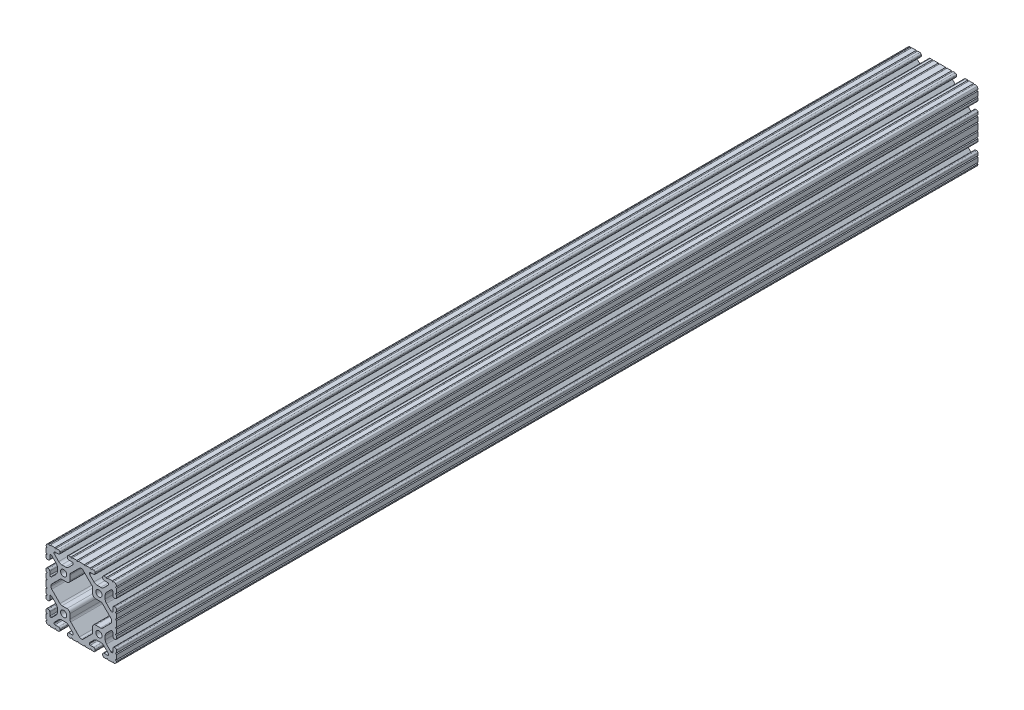
SolidWorks part; units mm, degrees
ref_plane "Front Plane" through (0, 0, 0) normal (0, 0, 1) x (1, 0, 0)
ref_plane "Top Plane" through (0, 0, 0) normal (0, 1, 0) x (1, 0, 0)
ref_plane "Right Plane" through (0, 0, 0) normal (1, 0, 0) x (0, 0, -1)
sketch "Sketch1" plane through (0, 0, 0) normal (0, 0, 1) x (1, 0, 0)
  line L0 (0, 38.1) -> (0, -38.1) construction
  line L1 (-38.1, -38.1) -> (38.1, -38.1) construction
  line L2 (-38.1, -38.1) -> (-38.1, 38.1) construction
  line L3 (-38.1, 38.1) -> (38.1, 38.1) construction
  line L4 (38.1, -38.1) -> (38.1, 38.1) construction
  line L5 (0, 38.1) -> (0, -38.1) construction
  line L6 (-38.1, 0) -> (38.1, 0) construction
  line L7 (-19.05, 19.05) -> (19.05, 19.05) construction
  line L8 (-19.05, 19.05) -> (-19.05, -19.05) construction
  line L9 (-19.05, -19.05) -> (19.05, -19.05) construction
  line L10 (19.05, 19.05) -> (19.05, -19.05) construction
  line L11 (-23.114, 38.1) -> (-23.114, -38.1) construction
  line L12 (-23.114, -38.1) -> (-14.986, 38.1) construction
  line L13 (-14.986, 38.1) -> (-14.986, -38.1) construction
  circle A0 centre (19.05, 19.05) radius 3.3274
  point P0 (0, 0)
  point P9 (0, 0)
  point P12 (-19.05, 0)
  line B0 (-11.3637, -22.8433) -> (-2.0515, -32.1555)
  line B1 (-12.2936, -15.4686) -> (-12.2936, -20.5983)
  line B2 (-20.769, -12.2936) -> (-15.4686, -12.2936)
  line B3 (-31.9021, -2.4756) -> (-23.0141, -11.3637)
  line B4 (-23.0141, 11.3637) -> (-31.9021, 2.4756)
  line B5 (-15.4686, 12.2936) -> (-20.769, 12.2936)
  line B6 (-12.2936, 20.5983) -> (-12.2936, 15.4686)
  line B7 (-2.0515, 32.1555) -> (-11.3637, 22.8433)
  line B8 (11.3637, 22.8433) -> (2.0515, 32.1555)
  line B9 (12.2936, 15.4686) -> (12.2936, 20.5983)
  line B10 (20.769, 12.2936) -> (15.4686, 12.2936)
  line B11 (31.9021, 2.4756) -> (23.0141, 11.3637)
  line B12 (23.0141, -11.3637) -> (31.9021, -2.4756)
  line B13 (15.4686, -12.2936) -> (20.769, -12.2936)
  line B14 (12.2936, -20.5983) -> (12.2936, -15.4686)
  line B15 (2.0515, -32.1555) -> (11.3637, -22.8433)
  line B16 (-4.7773, 38.1) -> (-9.6053, 38.1)
  line B17 (-11.1289, 38.1) -> (-13.4112, 38.1)
  line B18 (-14.986, 36.5252) -> (-14.986, 35.6108)
  line B19 (-13.4112, 34.036) -> (-9.652, 34.036)
  line B20 (-8.763, 33.147) -> (-8.763, 32.4935)
  line B21 (-9.0234, 31.8649) -> (-13.6907, 27.1976)
  line B22 (-17.0493, 25.8064) -> (-21.0507, 25.8064)
  line B23 (-24.4093, 27.1976) -> (-29.1002, 31.8885)
  line B24 (-29.337, 32.7207) -> (-29.337, 33.147)
  line B25 (-28.448, 34.036) -> (-24.6888, 34.036)
  line B26 (-23.114, 35.6108) -> (-23.114, 36.5252)
  line B27 (-24.6888, 38.1) -> (-27.0772, 38.1)
  line B28 (-28.6011, 38.1) -> (-33.4288, 38.1)
  line B29 (-38.1, 33.373) -> (-38.1, 28.5453)
  line B30 (-38.1, 27.0238) -> (-38.1, 24.6302)
  line B31 (-36.5252, 23.0554) -> (-35.6108, 23.0554)
  line B32 (-34.036, 24.6302) -> (-34.036, 28.448)
  line B33 (-33.147, 29.337) -> (-32.6643, 29.337)
  line B34 (-32.0357, 29.0766) -> (-27.1976, 24.2385)
  line B35 (-25.8064, 20.8799) -> (-25.8064, 17.2201)
  line B36 (-27.1976, 13.8615) -> (-31.9489, 9.1101)
  line B37 (-32.7869, 8.763) -> (-33.0603, 8.763)
  line B38 (-34.036, 9.7387) -> (-34.036, 13.4698)
  line B39 (-35.6108, 15.0446) -> (-36.5252, 15.0446)
  line B40 (-38.1, 13.4698) -> (-38.1, 11.075)
  line B41 (-38.1, 9.552) -> (-38.1, 4.7238)
  line B42 (-38.1, 3.2007) -> (-38.1, -3.2007)
  line B43 (-38.1, -4.7238) -> (-38.1, -9.552)
  line B44 (-38.1, -11.075) -> (-38.1, -13.4698)
  line B45 (-36.5252, -15.0446) -> (-35.6108, -15.0446)
  line B46 (-34.036, -13.4698) -> (-34.036, -9.7387)
  line B47 (-33.0603, -8.763) -> (-32.7869, -8.763)
  line B48 (-31.9489, -9.1101) -> (-27.1976, -13.8615)
  line B49 (-25.8064, -17.2201) -> (-25.8064, -20.8799)
  line B50 (-27.1976, -24.2385) -> (-32.0357, -29.0766)
  line B51 (-32.6643, -29.337) -> (-33.147, -29.337)
  line B52 (-34.036, -28.448) -> (-34.036, -24.6302)
  line B53 (-35.6108, -23.0554) -> (-36.5252, -23.0554)
  line B54 (-38.1, -24.6302) -> (-38.1, -27.0238)
  line B55 (-38.1, -28.5453) -> (-38.1, -33.373)
  line B56 (-33.4288, -38.1) -> (-28.6011, -38.1)
  line B57 (-27.0772, -38.1) -> (-24.6888, -38.1)
  line B58 (-23.114, -36.5252) -> (-23.114, -35.6108)
  line B59 (-24.6888, -34.036) -> (-28.448, -34.036)
  line B60 (-29.337, -33.147) -> (-29.337, -32.7207)
  line B61 (-29.1002, -31.8885) -> (-24.4093, -27.1976)
  line B62 (-21.0507, -25.8064) -> (-17.0493, -25.8064)
  line B63 (-13.6907, -27.1976) -> (-9.0234, -31.8649)
  line B64 (-8.763, -32.4935) -> (-8.763, -33.147)
  line B65 (-9.652, -34.036) -> (-13.4112, -34.036)
  line B66 (-14.986, -35.6108) -> (-14.986, -36.5252)
  line B67 (-13.4112, -38.1) -> (-11.1289, -38.1)
  line B68 (-9.6053, -38.1) -> (-4.7773, -38.1)
  line B69 (-3.2537, -38.1) -> (3.2537, -38.1)
  line B70 (4.7773, -38.1) -> (9.6053, -38.1)
  line B71 (11.1289, -38.1) -> (13.4112, -38.1)
  line B72 (14.986, -36.5252) -> (14.986, -35.6108)
  line B73 (13.4112, -34.036) -> (9.652, -34.036)
  line B74 (8.763, -33.147) -> (8.763, -32.4935)
  line B75 (9.0234, -31.8649) -> (13.6907, -27.1976)
  line B76 (17.0493, -25.8064) -> (21.0507, -25.8064)
  line B77 (24.4093, -27.1976) -> (29.1002, -31.8885)
  line B78 (29.337, -32.7207) -> (29.337, -33.147)
  line B79 (28.448, -34.036) -> (24.6888, -34.036)
  line B80 (23.114, -35.6108) -> (23.114, -36.5252)
  line B81 (24.6888, -38.1) -> (27.0772, -38.1)
  line B82 (28.6011, -38.1) -> (33.4288, -38.1)
  line B83 (38.1, -33.373) -> (38.1, -28.5453)
  line B84 (38.1, -27.0238) -> (38.1, -24.6302)
  line B85 (36.5252, -23.0554) -> (35.6108, -23.0554)
  line B86 (34.036, -24.6302) -> (34.036, -28.448)
  line B87 (33.147, -29.337) -> (32.6643, -29.337)
  line B88 (32.0357, -29.0766) -> (27.1976, -24.2385)
  line B89 (25.8064, -20.8799) -> (25.8064, -17.2201)
  line B90 (27.1976, -13.8615) -> (31.9489, -9.1101)
  line B91 (32.7869, -8.763) -> (33.0603, -8.763)
  line B92 (34.036, -9.7387) -> (34.036, -13.4698)
  line B93 (35.6108, -15.0446) -> (36.5252, -15.0446)
  line B94 (38.1, -13.4698) -> (38.1, -11.075)
  line B95 (38.1, -9.552) -> (38.1, -4.7238)
  line B96 (38.1, -3.2007) -> (38.1, 3.2007)
  line B97 (38.1, 4.7238) -> (38.1, 9.552)
  line B98 (38.1, 11.075) -> (38.1, 13.4698)
  line B99 (36.5252, 15.0446) -> (35.6108, 15.0446)
  line B100 (34.036, 13.4698) -> (34.036, 9.7387)
  line B101 (33.0603, 8.763) -> (32.7869, 8.763)
  line B102 (31.9489, 9.1101) -> (27.1976, 13.8615)
  line B103 (25.8064, 17.2201) -> (25.8064, 20.8799)
  line B104 (27.1976, 24.2385) -> (32.0357, 29.0766)
  line B105 (32.6643, 29.337) -> (33.147, 29.337)
  line B106 (34.036, 28.448) -> (34.036, 24.6302)
  line B107 (35.6108, 23.0554) -> (36.5252, 23.0554)
  line B108 (38.1, 24.6302) -> (38.1, 27.0238)
  line B109 (38.1, 28.5453) -> (38.1, 33.373)
  line B110 (33.4288, 38.1) -> (28.6011, 38.1)
  line B111 (27.0772, 38.1) -> (24.6888, 38.1)
  line B112 (23.114, 36.5252) -> (23.114, 35.6108)
  line B113 (24.6888, 34.036) -> (28.448, 34.036)
  line B114 (29.337, 33.147) -> (29.337, 32.7207)
  line B115 (29.1002, 31.8885) -> (24.4093, 27.1976)
  line B116 (21.0507, 25.8064) -> (17.0493, 25.8064)
  line B117 (13.6907, 27.1976) -> (9.0234, 31.8649)
  line B118 (8.763, 32.4935) -> (8.763, 33.147)
  line B119 (9.652, 34.036) -> (13.4112, 34.036)
  line B120 (14.986, 35.6108) -> (14.986, 36.5252)
  line B121 (13.4112, 38.1) -> (11.1289, 38.1)
  line B122 (9.6053, 38.1) -> (4.7773, 38.1)
  line B123 (3.2537, 38.1) -> (-3.2537, 38.1)
  circle B124 centre (-19.05, 19.05) radius 3.3274
  circle B125 centre (-19.05, -19.05) radius 3.3274
  circle B126 centre (19.05, -19.05) radius 3.3274
  circle B127 centre (19.05, 19.05) radius 3.3274
  arc B128 (0, -33.011) -> (2.0515, -32.1555) centre (-0.0139, -30.09) ccw
  arc B129 (-2.0515, -32.1555) -> (0, -33.011) centre (0.0139, -30.09) ccw
  arc B130 (-12.2936, -20.5983) -> (-11.3637, -22.8433) centre (-9.1186, -20.5983) ccw
  arc B131 (-12.2936, -15.4686) -> (-15.4686, -12.2936) centre (-15.4686, -15.4686) ccw
  arc B132 (-23.0141, -11.3637) -> (-20.769, -12.2936) centre (-20.769, -9.1186) ccw
  arc B133 (-32.7287, 0) -> (-31.9021, -2.4756) centre (-29.8367, -0.4102) ccw
  arc B134 (-31.9021, 2.4756) -> (-32.7287, 0) centre (-29.8367, 0.4102) ccw
  arc B135 (-20.769, 12.2936) -> (-23.0141, 11.3637) centre (-20.769, 9.1186) ccw
  arc B136 (-15.4686, 12.2936) -> (-12.2936, 15.4686) centre (-15.4686, 15.4686) ccw
  arc B137 (-11.3637, 22.8433) -> (-12.2936, 20.5983) centre (-9.1186, 20.5983) ccw
  arc B138 (0, 33.011) -> (-2.0515, 32.1555) centre (0.0139, 30.09) ccw
  arc B139 (2.0515, 32.1555) -> (0, 33.011) centre (-0.0139, 30.09) ccw
  arc B140 (12.2936, 20.5983) -> (11.3637, 22.8433) centre (9.1186, 20.5983) ccw
  arc B141 (12.2936, 15.4686) -> (15.4686, 12.2936) centre (15.4686, 15.4686) ccw
  arc B142 (23.0141, 11.3637) -> (20.769, 12.2936) centre (20.769, 9.1186) ccw
  arc B143 (32.7287, 0) -> (31.9021, 2.4756) centre (29.8367, 0.4102) ccw
  arc B144 (31.9021, -2.4756) -> (32.7287, 0) centre (29.8367, -0.4102) ccw
  arc B145 (20.769, -12.2936) -> (23.0141, -11.3637) centre (20.769, -9.1186) ccw
  arc B146 (15.4686, -12.2936) -> (12.2936, -15.4686) centre (15.4686, -15.4686) ccw
  arc B147 (11.3637, -22.8433) -> (12.2936, -20.5983) centre (9.1186, -20.5983) ccw
  arc B148 (-4.7773, 38.1) -> (-3.2537, 38.1) centre (-4.0155, 38.0824) ccw
  arc B149 (-11.1289, 38.1) -> (-9.6053, 38.1) centre (-10.3671, 38.0824) ccw
  arc B150 (-13.4112, 38.1) -> (-14.986, 36.5252) centre (-13.4112, 36.5252) ccw
  arc B151 (-14.986, 35.6108) -> (-13.4112, 34.036) centre (-13.4112, 35.6108) ccw
  arc B152 (-8.763, 33.147) -> (-9.652, 34.036) centre (-9.652, 33.147) ccw
  arc B153 (-9.0234, 31.8649) -> (-8.763, 32.4935) centre (-9.652, 32.4935) ccw
  arc B154 (-17.0493, 25.8064) -> (-13.6907, 27.1976) centre (-17.0493, 30.5562) ccw
  arc B155 (-24.4093, 27.1976) -> (-21.0507, 25.8064) centre (-21.0507, 30.5562) ccw
  arc B156 (-29.337, 32.7207) -> (-29.1002, 31.8885) centre (-28.4716, 32.5172) ccw
  arc B157 (-28.448, 34.036) -> (-29.337, 33.147) centre (-28.448, 33.147) ccw
  arc B158 (-24.6888, 34.036) -> (-23.114, 35.6108) centre (-24.6888, 35.6108) ccw
  arc B159 (-23.114, 36.5252) -> (-24.6888, 38.1) centre (-24.6888, 36.5252) ccw
  arc B160 (-28.6011, 38.1) -> (-27.0772, 38.1) centre (-27.8392, 38.0824) ccw
  arc B161 (-34.9527, 38.1) -> (-33.4288, 38.1) centre (-34.1907, 38.0824) ccw
  arc B162 (-34.9527, 38.1) -> (-37.0861, 37.1826) centre (-34.8521, 34.9266) ccw
  arc B163 (-37.0861, 37.1826) -> (-38.1, 34.8455) centre (-34.925, 34.8566) ccw
  arc B164 (-38.1, 33.373) -> (-38.1, 34.8455) centre (-37.9035, 34.1092) ccw
  arc B165 (-38.1, 27.0238) -> (-38.1, 28.5453) centre (-37.9035, 27.7845) ccw
  arc B166 (-38.1, 24.6302) -> (-36.5252, 23.0554) centre (-36.5252, 24.6302) ccw
  arc B167 (-35.6108, 23.0554) -> (-34.036, 24.6302) centre (-35.6108, 24.6302) ccw
  arc B168 (-33.147, 29.337) -> (-34.036, 28.448) centre (-33.147, 28.448) ccw
  arc B169 (-32.0357, 29.0766) -> (-32.6643, 29.337) centre (-32.6643, 28.448) ccw
  arc B170 (-25.8064, 20.8799) -> (-27.1976, 24.2385) centre (-30.5562, 20.8799) ccw
  arc B171 (-27.1976, 13.8615) -> (-25.8064, 17.2201) centre (-30.5562, 17.2201) ccw
  arc B172 (-32.7869, 8.763) -> (-31.9489, 9.1101) centre (-32.7869, 9.9481) ccw
  arc B173 (-34.036, 9.7387) -> (-33.0603, 8.763) centre (-33.0603, 9.7387) ccw
  arc B174 (-34.036, 13.4698) -> (-35.6108, 15.0446) centre (-35.6108, 13.4698) ccw
  arc B175 (-36.5252, 15.0446) -> (-38.1, 13.4698) centre (-36.5252, 13.4698) ccw
  arc B176 (-38.1, 9.552) -> (-38.1, 11.075) centre (-37.9035, 10.3135) ccw
  arc B177 (-38.1, 3.2007) -> (-38.1, 4.7238) centre (-37.9035, 3.9622) ccw
  arc B178 (-38.1, -4.7238) -> (-38.1, -3.2007) centre (-37.9035, -3.9622) ccw
  arc B179 (-38.1, -11.075) -> (-38.1, -9.552) centre (-37.9035, -10.3135) ccw
  arc B180 (-38.1, -13.4698) -> (-36.5252, -15.0446) centre (-36.5252, -13.4698) ccw
  arc B181 (-35.6108, -15.0446) -> (-34.036, -13.4698) centre (-35.6108, -13.4698) ccw
  arc B182 (-33.0603, -8.763) -> (-34.036, -9.7387) centre (-33.0603, -9.7387) ccw
  arc B183 (-31.9489, -9.1101) -> (-32.7869, -8.763) centre (-32.7869, -9.9481) ccw
  arc B184 (-25.8064, -17.2201) -> (-27.1976, -13.8615) centre (-30.5562, -17.2201) ccw
  arc B185 (-27.1976, -24.2385) -> (-25.8064, -20.8799) centre (-30.5562, -20.8799) ccw
  arc B186 (-32.6643, -29.337) -> (-32.0357, -29.0766) centre (-32.6643, -28.448) ccw
  arc B187 (-34.036, -28.448) -> (-33.147, -29.337) centre (-33.147, -28.448) ccw
  arc B188 (-34.036, -24.6302) -> (-35.6108, -23.0554) centre (-35.6108, -24.6302) ccw
  arc B189 (-36.5252, -23.0554) -> (-38.1, -24.6302) centre (-36.5252, -24.6302) ccw
  arc B190 (-38.1, -28.5453) -> (-38.1, -27.0238) centre (-37.9035, -27.7845) ccw
  arc B191 (-38.1, -34.8455) -> (-38.1, -33.373) centre (-37.9035, -34.1092) ccw
  arc B192 (-38.1, -34.8455) -> (-37.0861, -37.1826) centre (-34.925, -34.8566) ccw
  arc B193 (-37.0861, -37.1826) -> (-34.9527, -38.1) centre (-34.8521, -34.9266) ccw
  arc B194 (-33.4288, -38.1) -> (-34.9527, -38.1) centre (-34.1907, -38.0824) ccw
  arc B195 (-27.0772, -38.1) -> (-28.6011, -38.1) centre (-27.8392, -38.0824) ccw
  arc B196 (-24.6888, -38.1) -> (-23.114, -36.5252) centre (-24.6888, -36.5252) ccw
  arc B197 (-23.114, -35.6108) -> (-24.6888, -34.036) centre (-24.6888, -35.6108) ccw
  arc B198 (-29.337, -33.147) -> (-28.448, -34.036) centre (-28.448, -33.147) ccw
  arc B199 (-29.1002, -31.8885) -> (-29.337, -32.7207) centre (-28.4716, -32.5172) ccw
  arc B200 (-21.0507, -25.8064) -> (-24.4093, -27.1976) centre (-21.0507, -30.5562) ccw
  arc B201 (-13.6907, -27.1976) -> (-17.0493, -25.8064) centre (-17.0493, -30.5562) ccw
  arc B202 (-8.763, -32.4935) -> (-9.0234, -31.8649) centre (-9.652, -32.4935) ccw
  arc B203 (-9.652, -34.036) -> (-8.763, -33.147) centre (-9.652, -33.147) ccw
  arc B204 (-13.4112, -34.036) -> (-14.986, -35.6108) centre (-13.4112, -35.6108) ccw
  arc B205 (-14.986, -36.5252) -> (-13.4112, -38.1) centre (-13.4112, -36.5252) ccw
  arc B206 (-9.6053, -38.1) -> (-11.1289, -38.1) centre (-10.3671, -38.0824) ccw
  arc B207 (-3.2537, -38.1) -> (-4.7773, -38.1) centre (-4.0155, -38.0824) ccw
  arc B208 (4.7773, -38.1) -> (3.2537, -38.1) centre (4.0155, -38.0824) ccw
  arc B209 (11.1289, -38.1) -> (9.6053, -38.1) centre (10.3671, -38.0824) ccw
  arc B210 (13.4112, -38.1) -> (14.986, -36.5252) centre (13.4112, -36.5252) ccw
  arc B211 (14.986, -35.6108) -> (13.4112, -34.036) centre (13.4112, -35.6108) ccw
  arc B212 (8.763, -33.147) -> (9.652, -34.036) centre (9.652, -33.147) ccw
  arc B213 (9.0234, -31.8649) -> (8.763, -32.4935) centre (9.652, -32.4935) ccw
  arc B214 (17.0493, -25.8064) -> (13.6907, -27.1976) centre (17.0493, -30.5562) ccw
  arc B215 (24.4093, -27.1976) -> (21.0507, -25.8064) centre (21.0507, -30.5562) ccw
  arc B216 (29.337, -32.7207) -> (29.1002, -31.8885) centre (28.4716, -32.5172) ccw
  arc B217 (28.448, -34.036) -> (29.337, -33.147) centre (28.448, -33.147) ccw
  arc B218 (24.6888, -34.036) -> (23.114, -35.6108) centre (24.6888, -35.6108) ccw
  arc B219 (23.114, -36.5252) -> (24.6888, -38.1) centre (24.6888, -36.5252) ccw
  arc B220 (28.6011, -38.1) -> (27.0772, -38.1) centre (27.8392, -38.0824) ccw
  arc B221 (34.9527, -38.1) -> (33.4288, -38.1) centre (34.1907, -38.0824) ccw
  arc B222 (34.9527, -38.1) -> (37.0861, -37.1826) centre (34.8521, -34.9266) ccw
  arc B223 (37.0861, -37.1826) -> (38.1, -34.8455) centre (34.925, -34.8566) ccw
  arc B224 (38.1, -33.373) -> (38.1, -34.8455) centre (37.9035, -34.1092) ccw
  arc B225 (38.1, -27.0238) -> (38.1, -28.5453) centre (37.9035, -27.7845) ccw
  arc B226 (38.1, -24.6302) -> (36.5252, -23.0554) centre (36.5252, -24.6302) ccw
  arc B227 (35.6108, -23.0554) -> (34.036, -24.6302) centre (35.6108, -24.6302) ccw
  arc B228 (33.147, -29.337) -> (34.036, -28.448) centre (33.147, -28.448) ccw
  arc B229 (32.0357, -29.0766) -> (32.6643, -29.337) centre (32.6643, -28.448) ccw
  arc B230 (25.8064, -20.8799) -> (27.1976, -24.2385) centre (30.5562, -20.8799) ccw
  arc B231 (27.1976, -13.8615) -> (25.8064, -17.2201) centre (30.5562, -17.2201) ccw
  arc B232 (32.7869, -8.763) -> (31.9489, -9.1101) centre (32.7869, -9.9481) ccw
  arc B233 (34.036, -9.7387) -> (33.0603, -8.763) centre (33.0603, -9.7387) ccw
  arc B234 (34.036, -13.4698) -> (35.6108, -15.0446) centre (35.6108, -13.4698) ccw
  arc B235 (36.5252, -15.0446) -> (38.1, -13.4698) centre (36.5252, -13.4698) ccw
  arc B236 (38.1, -9.552) -> (38.1, -11.075) centre (37.9035, -10.3135) ccw
  arc B237 (38.1, -3.2007) -> (38.1, -4.7238) centre (37.9035, -3.9622) ccw
  arc B238 (38.1, 4.7238) -> (38.1, 3.2007) centre (37.9035, 3.9622) ccw
  arc B239 (38.1, 11.075) -> (38.1, 9.552) centre (37.9035, 10.3135) ccw
  arc B240 (38.1, 13.4698) -> (36.5252, 15.0446) centre (36.5252, 13.4698) ccw
  arc B241 (35.6108, 15.0446) -> (34.036, 13.4698) centre (35.6108, 13.4698) ccw
  arc B242 (33.0603, 8.763) -> (34.036, 9.7387) centre (33.0603, 9.7387) ccw
  arc B243 (31.9489, 9.1101) -> (32.7869, 8.763) centre (32.7869, 9.9481) ccw
  arc B244 (25.8064, 17.2201) -> (27.1976, 13.8615) centre (30.5562, 17.2201) ccw
  arc B245 (27.1976, 24.2385) -> (25.8064, 20.8799) centre (30.5562, 20.8799) ccw
  arc B246 (32.6643, 29.337) -> (32.0357, 29.0766) centre (32.6643, 28.448) ccw
  arc B247 (34.036, 28.448) -> (33.147, 29.337) centre (33.147, 28.448) ccw
  arc B248 (34.036, 24.6302) -> (35.6108, 23.0554) centre (35.6108, 24.6302) ccw
  arc B249 (36.5252, 23.0554) -> (38.1, 24.6302) centre (36.5252, 24.6302) ccw
  arc B250 (38.1, 28.5453) -> (38.1, 27.0238) centre (37.9035, 27.7845) ccw
  arc B251 (38.1, 34.8455) -> (38.1, 33.373) centre (37.9035, 34.1092) ccw
  arc B252 (38.1, 34.8455) -> (37.0861, 37.1826) centre (34.925, 34.8566) ccw
  arc B253 (37.0861, 37.1826) -> (34.9527, 38.1) centre (34.8521, 34.9266) ccw
  arc B254 (33.4288, 38.1) -> (34.9527, 38.1) centre (34.1907, 38.0824) ccw
  arc B255 (27.0772, 38.1) -> (28.6011, 38.1) centre (27.8392, 38.0824) ccw
  arc B256 (24.6888, 38.1) -> (23.114, 36.5252) centre (24.6888, 36.5252) ccw
  arc B257 (23.114, 35.6108) -> (24.6888, 34.036) centre (24.6888, 35.6108) ccw
  arc B258 (29.337, 33.147) -> (28.448, 34.036) centre (28.448, 33.147) ccw
  arc B259 (29.1002, 31.8885) -> (29.337, 32.7207) centre (28.4716, 32.5172) ccw
  arc B260 (21.0507, 25.8064) -> (24.4093, 27.1976) centre (21.0507, 30.5562) ccw
  arc B261 (13.6907, 27.1976) -> (17.0493, 25.8064) centre (17.0493, 30.5562) ccw
  arc B262 (8.763, 32.4935) -> (9.0234, 31.8649) centre (9.652, 32.4935) ccw
  arc B263 (9.652, 34.036) -> (8.763, 33.147) centre (9.652, 33.147) ccw
  arc B264 (13.4112, 34.036) -> (14.986, 35.6108) centre (13.4112, 35.6108) ccw
  arc B265 (14.986, 36.5252) -> (13.4112, 38.1) centre (13.4112, 36.5252) ccw
  arc B266 (9.6053, 38.1) -> (11.1289, 38.1) centre (10.3671, 38.0824) ccw
  arc B267 (3.2537, 38.1) -> (4.7773, 38.1) centre (4.0155, 38.0824) ccw
  dimension "Center Hole Diameter" = 6.6548
  dimension "Rail Width" = 76.2
  dimension "Rail Height" = 76.2
  dimension "T-Slot Width" = 8.128
sketch_block_instance "Block1-1"
sketch_block "Block1"
sketch "Sketch2" plane through (0, 0, 0) normal (1, 0, 0) x (0, 0, -1)
  line L0 (-465, 0) -> (465, 0) construction
  line L1 (-465, 38.1) -> (-465, -38.1) construction
  line L2 (-465, -38.1) -> (465, -38.1) construction
  line L3 (465, -38.1) -> (465, 38.1) construction
  line L4 (-363.4, 0) -> (-363.4, 38.1) construction
  line L5 (-363.4, 38.1) -> (363.4, 38.1) construction
  line L6 (363.4, 38.1) -> (363.4, 0) construction
  point P5 (363.4, 0)
  point P10 (-363.4, 0)
  dimension "D1" = 101.6
  dimension "Length" = 930
  dimension "D2" = 101.6
sketch "Sketch3" plane through (0, 0, 0) normal (0, 0, 1) x (1, 0, 0)
  line L0 (-11.3637, -22.8433) -> (-2.0515, -32.1555) construction
  line L1 (-12.2936, -15.4686) -> (-12.2936, -20.5983) construction
  line L2 (-20.769, -12.2936) -> (-15.4686, -12.2936) construction
  line L3 (-31.9021, -2.4756) -> (-23.0141, -11.3637) construction
  line L4 (-23.0141, 11.3637) -> (-31.9021, 2.4756) construction
  line L5 (-15.4686, 12.2936) -> (-20.769, 12.2936) construction
  line L6 (-12.2936, 20.5983) -> (-12.2936, 15.4686) construction
  line L7 (-2.0515, 32.1555) -> (-11.3637, 22.8433) construction
  line L8 (11.3637, 22.8433) -> (2.0515, 32.1555) construction
  line L9 (12.2936, 15.4686) -> (12.2936, 20.5983) construction
  line L10 (20.769, 12.2936) -> (15.4686, 12.2936) construction
  line L11 (31.9021, 2.4756) -> (23.0141, 11.3637) construction
  line L12 (23.0141, -11.3637) -> (31.9021, -2.4756) construction
  line L13 (15.4686, -12.2936) -> (20.769, -12.2936) construction
  line L14 (12.2936, -20.5983) -> (12.2936, -15.4686) construction
  line L15 (2.0515, -32.1555) -> (11.3637, -22.8433) construction
  line L16 (34.036, 28.448) -> (34.036, 24.6302) construction
  line L17 (35.6108, 23.0554) -> (36.5252, 23.0554) construction
  line L18 (38.1, 24.6302) -> (38.1, 27.0238) construction
  line L19 (38.1, 28.5453) -> (38.1, 33.373) construction
  line L20 (33.4288, 38.1) -> (28.6011, 38.1) construction
  line L21 (27.0772, 38.1) -> (24.6888, 38.1) construction
  line L22 (23.114, 36.5252) -> (23.114, 35.6108) construction
  line L23 (24.6888, 34.036) -> (28.448, 34.036) construction
  line L24 (29.337, 33.147) -> (29.337, 32.7207) construction
  line L25 (29.1002, 31.8885) -> (24.4093, 27.1976) construction
  line L26 (21.0507, 25.8064) -> (17.0493, 25.8064) construction
  line L27 (13.6907, 27.1976) -> (9.0234, 31.8649) construction
  line L28 (8.763, 32.4935) -> (8.763, 33.147) construction
  line L29 (9.652, 34.036) -> (13.4112, 34.036) construction
  line L30 (14.986, 35.6108) -> (14.986, 36.5252) construction
  line L31 (13.4112, 38.1) -> (11.1289, 38.1) construction
  line L32 (9.6053, 38.1) -> (4.7773, 38.1) construction
  line L33 (3.2537, 38.1) -> (-3.2537, 38.1) construction
  line L34 (-4.7773, 38.1) -> (-9.6053, 38.1) construction
  line L35 (-11.1289, 38.1) -> (-13.4112, 38.1) construction
  line L36 (-14.986, 36.5252) -> (-14.986, 35.6108) construction
  line L37 (-13.4112, 34.036) -> (-9.652, 34.036) construction
  line L38 (-8.763, 33.147) -> (-8.763, 32.4935) construction
  line L39 (-9.0234, 31.8649) -> (-13.6907, 27.1976) construction
  line L40 (-17.0493, 25.8064) -> (-21.0507, 25.8064) construction
  line L41 (-24.4093, 27.1976) -> (-29.1002, 31.8885) construction
  line L42 (-29.337, 32.7207) -> (-29.337, 33.147) construction
  line L43 (-28.448, 34.036) -> (-24.6888, 34.036) construction
  line L44 (-23.114, 35.6108) -> (-23.114, 36.5252) construction
  line L45 (-24.6888, 38.1) -> (-27.0772, 38.1) construction
  line L46 (-28.6011, 38.1) -> (-33.4288, 38.1) construction
  line L47 (-38.1, 33.373) -> (-38.1, 28.5453) construction
  line L48 (-38.1, 27.0238) -> (-38.1, 24.6302) construction
  line L49 (-36.5252, 23.0554) -> (-35.6108, 23.0554) construction
  line L50 (-34.036, 24.6302) -> (-34.036, 28.448) construction
  line L51 (-33.147, 29.337) -> (-32.6643, 29.337) construction
  line L52 (-32.0357, 29.0766) -> (-27.1976, 24.2385) construction
  line L53 (-25.8064, 20.8799) -> (-25.8064, 17.2201) construction
  line L54 (-27.1976, 13.8615) -> (-31.9489, 9.1101) construction
  line L55 (-32.7869, 8.763) -> (-33.0603, 8.763) construction
  line L56 (-34.036, 9.7387) -> (-34.036, 13.4698) construction
  line L57 (-35.6108, 15.0446) -> (-36.5252, 15.0446) construction
  line L58 (-38.1, 13.4698) -> (-38.1, 11.075) construction
  line L59 (-38.1, 9.552) -> (-38.1, 4.7238) construction
  line L60 (-38.1, 3.2007) -> (-38.1, -3.2007) construction
  line L61 (-38.1, -4.7238) -> (-38.1, -9.552) construction
  line L62 (-38.1, -11.075) -> (-38.1, -13.4698) construction
  line L63 (-36.5252, -15.0446) -> (-35.6108, -15.0446) construction
  line L64 (-34.036, -13.4698) -> (-34.036, -9.7387) construction
  line L65 (-33.0603, -8.763) -> (-32.7869, -8.763) construction
  line L66 (-31.9489, -9.1101) -> (-27.1976, -13.8615) construction
  line L67 (-25.8064, -17.2201) -> (-25.8064, -20.8799) construction
  line L68 (-27.1976, -24.2385) -> (-32.0357, -29.0766) construction
  line L69 (-32.6643, -29.337) -> (-33.147, -29.337) construction
  line L70 (-34.036, -28.448) -> (-34.036, -24.6302) construction
  line L71 (-35.6108, -23.0554) -> (-36.5252, -23.0554) construction
  line L72 (-38.1, -24.6302) -> (-38.1, -27.0238) construction
  line L73 (-38.1, -28.5453) -> (-38.1, -33.373) construction
  line L74 (-33.4288, -38.1) -> (-28.6011, -38.1) construction
  line L75 (-27.0772, -38.1) -> (-24.6888, -38.1) construction
  line L76 (-23.114, -36.5252) -> (-23.114, -35.6108) construction
  line L77 (-24.6888, -34.036) -> (-28.448, -34.036) construction
  line L78 (-29.337, -33.147) -> (-29.337, -32.7207) construction
  line L79 (-29.1002, -31.8885) -> (-24.4093, -27.1976) construction
  line L80 (-21.0507, -25.8064) -> (-17.0493, -25.8064) construction
  line L81 (-13.6907, -27.1976) -> (-9.0234, -31.8649) construction
  line L82 (-8.763, -32.4935) -> (-8.763, -33.147) construction
  line L83 (-9.652, -34.036) -> (-13.4112, -34.036) construction
  line L84 (-14.986, -35.6108) -> (-14.986, -36.5252) construction
  line L85 (-13.4112, -38.1) -> (-11.1289, -38.1) construction
  line L86 (-9.6053, -38.1) -> (-4.7773, -38.1) construction
  line L87 (-3.2537, -38.1) -> (3.2537, -38.1) construction
  line L88 (4.7773, -38.1) -> (9.6053, -38.1) construction
  line L89 (11.1289, -38.1) -> (13.4112, -38.1) construction
  line L90 (14.986, -36.5252) -> (14.986, -35.6108) construction
  line L91 (13.4112, -34.036) -> (9.652, -34.036) construction
  line L92 (8.763, -33.147) -> (8.763, -32.4935) construction
  line L93 (9.0234, -31.8649) -> (13.6907, -27.1976) construction
  line L94 (17.0493, -25.8064) -> (21.0507, -25.8064) construction
  line L95 (24.4093, -27.1976) -> (29.1002, -31.8885) construction
  line L96 (29.337, -32.7207) -> (29.337, -33.147) construction
  line L97 (28.448, -34.036) -> (24.6888, -34.036) construction
  line L98 (23.114, -35.6108) -> (23.114, -36.5252) construction
  line L99 (24.6888, -38.1) -> (27.0772, -38.1) construction
  line L100 (28.6011, -38.1) -> (33.4288, -38.1) construction
  line L101 (38.1, -33.373) -> (38.1, -28.5453) construction
  line L102 (38.1, -27.0238) -> (38.1, -24.6302) construction
  line L103 (36.5252, -23.0554) -> (35.6108, -23.0554) construction
  line L104 (34.036, -24.6302) -> (34.036, -28.448) construction
  line L105 (33.147, -29.337) -> (32.6643, -29.337) construction
  line L106 (32.0357, -29.0766) -> (27.1976, -24.2385) construction
  line L107 (25.8064, -20.8799) -> (25.8064, -17.2201) construction
  line L108 (27.1976, -13.8615) -> (31.9489, -9.1101) construction
  line L109 (32.7869, -8.763) -> (33.0603, -8.763) construction
  line L110 (34.036, -9.7387) -> (34.036, -13.4698) construction
  line L111 (35.6108, -15.0446) -> (36.5252, -15.0446) construction
  line L112 (38.1, -13.4698) -> (38.1, -11.075) construction
  line L113 (38.1, -9.552) -> (38.1, -4.7238) construction
  line L114 (38.1, -3.2007) -> (38.1, 3.2007) construction
  line L115 (38.1, 4.7238) -> (38.1, 9.552) construction
  line L116 (38.1, 11.075) -> (38.1, 13.4698) construction
  line L117 (36.5252, 15.0446) -> (35.6108, 15.0446) construction
  line L118 (34.036, 13.4698) -> (34.036, 9.7387) construction
  line L119 (33.0603, 8.763) -> (32.7869, 8.763) construction
  line L120 (31.9489, 9.1101) -> (27.1976, 13.8615) construction
  line L121 (25.8064, 17.2201) -> (25.8064, 20.8799) construction
  line L122 (27.1976, 24.2385) -> (32.0357, 29.0766) construction
  line L123 (32.6643, 29.337) -> (33.147, 29.337) construction
  line L124 (-11.3637, -22.8433) -> (-2.0515, -32.1555)
  line L125 (-12.2936, -15.4686) -> (-12.2936, -20.5983)
  line L126 (-20.769, -12.2936) -> (-15.4686, -12.2936)
  line L127 (-31.9021, -2.4756) -> (-23.0141, -11.3637)
  line L128 (-23.0141, 11.3637) -> (-31.9021, 2.4756)
  line L129 (-15.4686, 12.2936) -> (-20.769, 12.2936)
  line L130 (-12.2936, 20.5983) -> (-12.2936, 15.4686)
  line L131 (-2.0515, 32.1555) -> (-11.3637, 22.8433)
  line L132 (11.3637, 22.8433) -> (2.0515, 32.1555)
  line L133 (12.2936, 15.4686) -> (12.2936, 20.5983)
  line L134 (20.769, 12.2936) -> (15.4686, 12.2936)
  line L135 (31.9021, 2.4756) -> (23.0141, 11.3637)
  line L136 (23.0141, -11.3637) -> (31.9021, -2.4756)
  line L137 (15.4686, -12.2936) -> (20.769, -12.2936)
  line L138 (12.2936, -20.5983) -> (12.2936, -15.4686)
  line L139 (2.0515, -32.1555) -> (11.3637, -22.8433)
  line L140 (34.036, 28.448) -> (34.036, 24.6302)
  line L141 (35.6108, 23.0554) -> (36.5252, 23.0554)
  line L142 (38.1, 24.6302) -> (38.1, 27.0238)
  line L143 (38.1, 28.5453) -> (38.1, 33.373)
  line L144 (33.4288, 38.1) -> (28.6011, 38.1)
  line L145 (27.0772, 38.1) -> (24.6888, 38.1)
  line L146 (23.114, 36.5252) -> (23.114, 35.6108)
  line L147 (24.6888, 34.036) -> (28.448, 34.036)
  line L148 (29.337, 33.147) -> (29.337, 32.7207)
  line L149 (29.1002, 31.8885) -> (24.4093, 27.1976)
  line L150 (21.0507, 25.8064) -> (17.0493, 25.8064)
  line L151 (13.6907, 27.1976) -> (9.0234, 31.8649)
  line L152 (8.763, 32.4935) -> (8.763, 33.147)
  line L153 (9.652, 34.036) -> (13.4112, 34.036)
  line L154 (14.986, 35.6108) -> (14.986, 36.5252)
  line L155 (13.4112, 38.1) -> (11.1289, 38.1)
  line L156 (9.6053, 38.1) -> (4.7773, 38.1)
  line L157 (3.2537, 38.1) -> (-3.2537, 38.1)
  line L158 (-4.7773, 38.1) -> (-9.6053, 38.1)
  line L159 (-11.1289, 38.1) -> (-13.4112, 38.1)
  line L160 (-14.986, 36.5252) -> (-14.986, 35.6108)
  line L161 (-13.4112, 34.036) -> (-9.652, 34.036)
  line L162 (-8.763, 33.147) -> (-8.763, 32.4935)
  line L163 (-9.0234, 31.8649) -> (-13.6907, 27.1976)
  line L164 (-17.0493, 25.8064) -> (-21.0507, 25.8064)
  line L165 (-24.4093, 27.1976) -> (-29.1002, 31.8885)
  line L166 (-29.337, 32.7207) -> (-29.337, 33.147)
  line L167 (-28.448, 34.036) -> (-24.6888, 34.036)
  line L168 (-23.114, 35.6108) -> (-23.114, 36.5252)
  line L169 (-24.6888, 38.1) -> (-27.0772, 38.1)
  line L170 (-28.6011, 38.1) -> (-33.4288, 38.1)
  line L171 (-38.1, 33.373) -> (-38.1, 28.5453)
  line L172 (-38.1, 27.0238) -> (-38.1, 24.6302)
  line L173 (-36.5252, 23.0554) -> (-35.6108, 23.0554)
  line L174 (-34.036, 24.6302) -> (-34.036, 28.448)
  line L175 (-33.147, 29.337) -> (-32.6643, 29.337)
  line L176 (-32.0357, 29.0766) -> (-27.1976, 24.2385)
  line L177 (-25.8064, 20.8799) -> (-25.8064, 17.2201)
  line L178 (-27.1976, 13.8615) -> (-31.9489, 9.1101)
  line L179 (-32.7869, 8.763) -> (-33.0603, 8.763)
  line L180 (-34.036, 9.7387) -> (-34.036, 13.4698)
  line L181 (-35.6108, 15.0446) -> (-36.5252, 15.0446)
  line L182 (-38.1, 13.4698) -> (-38.1, 11.075)
  line L183 (-38.1, 9.552) -> (-38.1, 4.7238)
  line L184 (-38.1, 3.2007) -> (-38.1, -3.2007)
  line L185 (-38.1, -4.7238) -> (-38.1, -9.552)
  line L186 (-38.1, -11.075) -> (-38.1, -13.4698)
  line L187 (-36.5252, -15.0446) -> (-35.6108, -15.0446)
  line L188 (-34.036, -13.4698) -> (-34.036, -9.7387)
  line L189 (-33.0603, -8.763) -> (-32.7869, -8.763)
  line L190 (-31.9489, -9.1101) -> (-27.1976, -13.8615)
  line L191 (-25.8064, -17.2201) -> (-25.8064, -20.8799)
  line L192 (-27.1976, -24.2385) -> (-32.0357, -29.0766)
  line L193 (-32.6643, -29.337) -> (-33.147, -29.337)
  line L194 (-34.036, -28.448) -> (-34.036, -24.6302)
  line L195 (-35.6108, -23.0554) -> (-36.5252, -23.0554)
  line L196 (-38.1, -24.6302) -> (-38.1, -27.0238)
  line L197 (-38.1, -28.5453) -> (-38.1, -33.373)
  line L198 (-33.4288, -38.1) -> (-28.6011, -38.1)
  line L199 (-27.0772, -38.1) -> (-24.6888, -38.1)
  line L200 (-23.114, -36.5252) -> (-23.114, -35.6108)
  line L201 (-24.6888, -34.036) -> (-28.448, -34.036)
  line L202 (-29.337, -33.147) -> (-29.337, -32.7207)
  line L203 (-29.1002, -31.8885) -> (-24.4093, -27.1976)
  line L204 (-21.0507, -25.8064) -> (-17.0493, -25.8064)
  line L205 (-13.6907, -27.1976) -> (-9.0234, -31.8649)
  line L206 (-8.763, -32.4935) -> (-8.763, -33.147)
  line L207 (-9.652, -34.036) -> (-13.4112, -34.036)
  line L208 (-14.986, -35.6108) -> (-14.986, -36.5252)
  line L209 (-13.4112, -38.1) -> (-11.1289, -38.1)
  line L210 (-9.6053, -38.1) -> (-4.7773, -38.1)
  line L211 (-3.2537, -38.1) -> (3.2537, -38.1)
  line L212 (4.7773, -38.1) -> (9.6053, -38.1)
  line L213 (11.1289, -38.1) -> (13.4112, -38.1)
  line L214 (14.986, -36.5252) -> (14.986, -35.6108)
  line L215 (13.4112, -34.036) -> (9.652, -34.036)
  line L216 (8.763, -33.147) -> (8.763, -32.4935)
  line L217 (9.0234, -31.8649) -> (13.6907, -27.1976)
  line L218 (17.0493, -25.8064) -> (21.0507, -25.8064)
  line L219 (24.4093, -27.1976) -> (29.1002, -31.8885)
  line L220 (29.337, -32.7207) -> (29.337, -33.147)
  line L221 (28.448, -34.036) -> (24.6888, -34.036)
  line L222 (23.114, -35.6108) -> (23.114, -36.5252)
  line L223 (24.6888, -38.1) -> (27.0772, -38.1)
  line L224 (28.6011, -38.1) -> (33.4288, -38.1)
  line L225 (38.1, -33.373) -> (38.1, -28.5453)
  line L226 (38.1, -27.0238) -> (38.1, -24.6302)
  line L227 (36.5252, -23.0554) -> (35.6108, -23.0554)
  line L228 (34.036, -24.6302) -> (34.036, -28.448)
  line L229 (33.147, -29.337) -> (32.6643, -29.337)
  line L230 (32.0357, -29.0766) -> (27.1976, -24.2385)
  line L231 (25.8064, -20.8799) -> (25.8064, -17.2201)
  line L232 (27.1976, -13.8615) -> (31.9489, -9.1101)
  line L233 (32.7869, -8.763) -> (33.0603, -8.763)
  line L234 (34.036, -9.7387) -> (34.036, -13.4698)
  line L235 (35.6108, -15.0446) -> (36.5252, -15.0446)
  line L236 (38.1, -13.4698) -> (38.1, -11.075)
  line L237 (38.1, -9.552) -> (38.1, -4.7238)
  line L238 (38.1, -3.2007) -> (38.1, 3.2007)
  line L239 (38.1, 4.7238) -> (38.1, 9.552)
  line L240 (38.1, 11.075) -> (38.1, 13.4698)
  line L241 (36.5252, 15.0446) -> (35.6108, 15.0446)
  line L242 (34.036, 13.4698) -> (34.036, 9.7387)
  line L243 (33.0603, 8.763) -> (32.7869, 8.763)
  line L244 (31.9489, 9.1101) -> (27.1976, 13.8615)
  line L245 (25.8064, 17.2201) -> (25.8064, 20.8799)
  line L246 (27.1976, 24.2385) -> (32.0357, 29.0766)
  line L247 (32.6643, 29.337) -> (33.147, 29.337)
  arc A0 (-2.0515, -32.1555) -> (0, -33.011) centre (0.0139, -30.09) ccw construction
  circle A1 centre (19.05, 19.05) radius 3.3274
  circle A2 centre (19.05, 19.05) radius 3.3274
  arc A3 (-12.2936, -20.5983) -> (-11.3637, -22.8433) centre (-9.1186, -20.5983) ccw construction
  arc A4 (-12.2936, -15.4686) -> (-15.4686, -12.2936) centre (-15.4686, -15.4686) ccw construction
  arc A5 (-23.0141, -11.3637) -> (-20.769, -12.2936) centre (-20.769, -9.1186) ccw construction
  arc A6 (-32.7287, 0) -> (-31.9021, -2.4756) centre (-29.8367, -0.4102) ccw construction
  arc A7 (-31.9021, 2.4756) -> (-32.7287, 0) centre (-29.8367, 0.4102) ccw construction
  arc A8 (-20.769, 12.2936) -> (-23.0141, 11.3637) centre (-20.769, 9.1186) ccw construction
  arc A9 (-15.4686, 12.2936) -> (-12.2936, 15.4686) centre (-15.4686, 15.4686) ccw construction
  arc A10 (-11.3637, 22.8433) -> (-12.2936, 20.5983) centre (-9.1186, 20.5983) ccw construction
  arc A11 (0, 33.011) -> (-2.0515, 32.1555) centre (0.0139, 30.09) ccw construction
  arc A12 (2.0515, 32.1555) -> (0, 33.011) centre (-0.0139, 30.09) ccw construction
  arc A13 (12.2936, 20.5983) -> (11.3637, 22.8433) centre (9.1186, 20.5983) ccw construction
  arc A14 (12.2936, 15.4686) -> (15.4686, 12.2936) centre (15.4686, 15.4686) ccw construction
  arc A15 (23.0141, 11.3637) -> (20.769, 12.2936) centre (20.769, 9.1186) ccw construction
  arc A16 (32.7287, 0) -> (31.9021, 2.4756) centre (29.8367, 0.4102) ccw construction
  arc A17 (31.9021, -2.4756) -> (32.7287, 0) centre (29.8367, -0.4102) ccw construction
  arc A18 (20.769, -12.2936) -> (23.0141, -11.3637) centre (20.769, -9.1186) ccw construction
  arc A19 (15.4686, -12.2936) -> (12.2936, -15.4686) centre (15.4686, -15.4686) ccw construction
  arc A20 (11.3637, -22.8433) -> (12.2936, -20.5983) centre (9.1186, -20.5983) ccw construction
  arc A21 (0, -33.011) -> (2.0515, -32.1555) centre (-0.0139, -30.09) ccw construction
  circle A22 centre (-19.05, 19.05) radius 3.3274 construction
  circle A23 centre (19.05, -19.05) radius 3.3274 construction
  circle A24 centre (-19.05, -19.05) radius 3.3274 construction
  circle A25 centre (19.05, 19.05) radius 3.3274 construction
  arc A26 (34.036, 24.6302) -> (35.6108, 23.0554) centre (35.6108, 24.6302) ccw construction
  arc A27 (36.5252, 23.0554) -> (38.1, 24.6302) centre (36.5252, 24.6302) ccw construction
  arc A28 (38.1, 28.5453) -> (38.1, 27.0238) centre (37.9035, 27.7845) ccw construction
  arc A29 (38.1, 34.8455) -> (38.1, 33.373) centre (37.9035, 34.1092) ccw construction
  arc A30 (38.1, 34.8455) -> (37.0861, 37.1826) centre (34.925, 34.8566) ccw construction
  arc A31 (37.0861, 37.1826) -> (34.9527, 38.1) centre (34.8521, 34.9266) ccw construction
  arc A32 (33.4288, 38.1) -> (34.9527, 38.1) centre (34.1907, 38.0824) ccw construction
  arc A33 (27.0772, 38.1) -> (28.6011, 38.1) centre (27.8392, 38.0824) ccw construction
  arc A34 (24.6888, 38.1) -> (23.114, 36.5252) centre (24.6888, 36.5252) ccw construction
  arc A35 (23.114, 35.6108) -> (24.6888, 34.036) centre (24.6888, 35.6108) ccw construction
  arc A36 (29.337, 33.147) -> (28.448, 34.036) centre (28.448, 33.147) ccw construction
  arc A37 (29.1002, 31.8885) -> (29.337, 32.7207) centre (28.4716, 32.5172) ccw construction
  arc A38 (21.0507, 25.8064) -> (24.4093, 27.1976) centre (21.0507, 30.5562) ccw construction
  arc A39 (13.6907, 27.1976) -> (17.0493, 25.8064) centre (17.0493, 30.5562) ccw construction
  arc A40 (8.763, 32.4935) -> (9.0234, 31.8649) centre (9.652, 32.4935) ccw construction
  arc A41 (9.652, 34.036) -> (8.763, 33.147) centre (9.652, 33.147) ccw construction
  arc A42 (13.4112, 34.036) -> (14.986, 35.6108) centre (13.4112, 35.6108) ccw construction
  arc A43 (14.986, 36.5252) -> (13.4112, 38.1) centre (13.4112, 36.5252) ccw construction
  arc A44 (9.6053, 38.1) -> (11.1289, 38.1) centre (10.3671, 38.0824) ccw construction
  arc A45 (3.2537, 38.1) -> (4.7773, 38.1) centre (4.0155, 38.0824) ccw construction
  arc A46 (-4.7773, 38.1) -> (-3.2537, 38.1) centre (-4.0155, 38.0824) ccw construction
  arc A47 (-11.1289, 38.1) -> (-9.6053, 38.1) centre (-10.3671, 38.0824) ccw construction
  arc A48 (-13.4112, 38.1) -> (-14.986, 36.5252) centre (-13.4112, 36.5252) ccw construction
  arc A49 (-14.986, 35.6108) -> (-13.4112, 34.036) centre (-13.4112, 35.6108) ccw construction
  arc A50 (-8.763, 33.147) -> (-9.652, 34.036) centre (-9.652, 33.147) ccw construction
  arc A51 (-9.0234, 31.8649) -> (-8.763, 32.4935) centre (-9.652, 32.4935) ccw construction
  arc A52 (-17.0493, 25.8064) -> (-13.6907, 27.1976) centre (-17.0493, 30.5562) ccw construction
  arc A53 (-24.4093, 27.1976) -> (-21.0507, 25.8064) centre (-21.0507, 30.5562) ccw construction
  arc A54 (-29.337, 32.7207) -> (-29.1002, 31.8885) centre (-28.4716, 32.5172) ccw construction
  arc A55 (-28.448, 34.036) -> (-29.337, 33.147) centre (-28.448, 33.147) ccw construction
  arc A56 (-24.6888, 34.036) -> (-23.114, 35.6108) centre (-24.6888, 35.6108) ccw construction
  arc A57 (-23.114, 36.5252) -> (-24.6888, 38.1) centre (-24.6888, 36.5252) ccw construction
  arc A58 (-28.6011, 38.1) -> (-27.0772, 38.1) centre (-27.8392, 38.0824) ccw construction
  arc A59 (-34.9527, 38.1) -> (-33.4288, 38.1) centre (-34.1907, 38.0824) ccw construction
  arc A60 (-34.9527, 38.1) -> (-37.0861, 37.1826) centre (-34.8521, 34.9266) ccw construction
  arc A61 (-37.0861, 37.1826) -> (-38.1, 34.8455) centre (-34.925, 34.8566) ccw construction
  arc A62 (-38.1, 33.373) -> (-38.1, 34.8455) centre (-37.9035, 34.1092) ccw construction
  arc A63 (-38.1, 27.0238) -> (-38.1, 28.5453) centre (-37.9035, 27.7845) ccw construction
  arc A64 (-38.1, 24.6302) -> (-36.5252, 23.0554) centre (-36.5252, 24.6302) ccw construction
  arc A65 (-35.6108, 23.0554) -> (-34.036, 24.6302) centre (-35.6108, 24.6302) ccw construction
  arc A66 (-33.147, 29.337) -> (-34.036, 28.448) centre (-33.147, 28.448) ccw construction
  arc A67 (-32.0357, 29.0766) -> (-32.6643, 29.337) centre (-32.6643, 28.448) ccw construction
  arc A68 (-25.8064, 20.8799) -> (-27.1976, 24.2385) centre (-30.5562, 20.8799) ccw construction
  arc A69 (-27.1976, 13.8615) -> (-25.8064, 17.2201) centre (-30.5562, 17.2201) ccw construction
  arc A70 (-32.7869, 8.763) -> (-31.9489, 9.1101) centre (-32.7869, 9.9481) ccw construction
  arc A71 (-34.036, 9.7387) -> (-33.0603, 8.763) centre (-33.0603, 9.7387) ccw construction
  arc A72 (-34.036, 13.4698) -> (-35.6108, 15.0446) centre (-35.6108, 13.4698) ccw construction
  arc A73 (-36.5252, 15.0446) -> (-38.1, 13.4698) centre (-36.5252, 13.4698) ccw construction
  arc A74 (-38.1, 9.552) -> (-38.1, 11.075) centre (-37.9035, 10.3135) ccw construction
  arc A75 (-38.1, 3.2007) -> (-38.1, 4.7238) centre (-37.9035, 3.9622) ccw construction
  arc A76 (-38.1, -4.7238) -> (-38.1, -3.2007) centre (-37.9035, -3.9622) ccw construction
  arc A77 (-38.1, -11.075) -> (-38.1, -9.552) centre (-37.9035, -10.3135) ccw construction
  arc A78 (-38.1, -13.4698) -> (-36.5252, -15.0446) centre (-36.5252, -13.4698) ccw construction
  arc A79 (-35.6108, -15.0446) -> (-34.036, -13.4698) centre (-35.6108, -13.4698) ccw construction
  arc A80 (-33.0603, -8.763) -> (-34.036, -9.7387) centre (-33.0603, -9.7387) ccw construction
  arc A81 (-31.9489, -9.1101) -> (-32.7869, -8.763) centre (-32.7869, -9.9481) ccw construction
  arc A82 (-25.8064, -17.2201) -> (-27.1976, -13.8615) centre (-30.5562, -17.2201) ccw construction
  arc A83 (-27.1976, -24.2385) -> (-25.8064, -20.8799) centre (-30.5562, -20.8799) ccw construction
  arc A84 (-32.6643, -29.337) -> (-32.0357, -29.0766) centre (-32.6643, -28.448) ccw construction
  arc A85 (-34.036, -28.448) -> (-33.147, -29.337) centre (-33.147, -28.448) ccw construction
  arc A86 (-34.036, -24.6302) -> (-35.6108, -23.0554) centre (-35.6108, -24.6302) ccw construction
  arc A87 (-36.5252, -23.0554) -> (-38.1, -24.6302) centre (-36.5252, -24.6302) ccw construction
  arc A88 (-38.1, -28.5453) -> (-38.1, -27.0238) centre (-37.9035, -27.7845) ccw construction
  arc A89 (-38.1, -34.8455) -> (-38.1, -33.373) centre (-37.9035, -34.1092) ccw construction
  arc A90 (-38.1, -34.8455) -> (-37.0861, -37.1826) centre (-34.925, -34.8566) ccw construction
  arc A91 (-37.0861, -37.1826) -> (-34.9527, -38.1) centre (-34.8521, -34.9266) ccw construction
  arc A92 (-33.4288, -38.1) -> (-34.9527, -38.1) centre (-34.1907, -38.0824) ccw construction
  arc A93 (-27.0772, -38.1) -> (-28.6011, -38.1) centre (-27.8392, -38.0824) ccw construction
  arc A94 (-24.6888, -38.1) -> (-23.114, -36.5252) centre (-24.6888, -36.5252) ccw construction
  arc A95 (-23.114, -35.6108) -> (-24.6888, -34.036) centre (-24.6888, -35.6108) ccw construction
  arc A96 (-29.337, -33.147) -> (-28.448, -34.036) centre (-28.448, -33.147) ccw construction
  arc A97 (-29.1002, -31.8885) -> (-29.337, -32.7207) centre (-28.4716, -32.5172) ccw construction
  arc A98 (-21.0507, -25.8064) -> (-24.4093, -27.1976) centre (-21.0507, -30.5562) ccw construction
  arc A99 (-13.6907, -27.1976) -> (-17.0493, -25.8064) centre (-17.0493, -30.5562) ccw construction
  arc A100 (-8.763, -32.4935) -> (-9.0234, -31.8649) centre (-9.652, -32.4935) ccw construction
  arc A101 (-9.652, -34.036) -> (-8.763, -33.147) centre (-9.652, -33.147) ccw construction
  arc A102 (-13.4112, -34.036) -> (-14.986, -35.6108) centre (-13.4112, -35.6108) ccw construction
  arc A103 (-14.986, -36.5252) -> (-13.4112, -38.1) centre (-13.4112, -36.5252) ccw construction
  arc A104 (-9.6053, -38.1) -> (-11.1289, -38.1) centre (-10.3671, -38.0824) ccw construction
  arc A105 (-3.2537, -38.1) -> (-4.7773, -38.1) centre (-4.0155, -38.0824) ccw construction
  arc A106 (4.7773, -38.1) -> (3.2537, -38.1) centre (4.0155, -38.0824) ccw construction
  arc A107 (11.1289, -38.1) -> (9.6053, -38.1) centre (10.3671, -38.0824) ccw construction
  arc A108 (13.4112, -38.1) -> (14.986, -36.5252) centre (13.4112, -36.5252) ccw construction
  arc A109 (14.986, -35.6108) -> (13.4112, -34.036) centre (13.4112, -35.6108) ccw construction
  arc A110 (8.763, -33.147) -> (9.652, -34.036) centre (9.652, -33.147) ccw construction
  arc A111 (9.0234, -31.8649) -> (8.763, -32.4935) centre (9.652, -32.4935) ccw construction
  arc A112 (17.0493, -25.8064) -> (13.6907, -27.1976) centre (17.0493, -30.5562) ccw construction
  arc A113 (24.4093, -27.1976) -> (21.0507, -25.8064) centre (21.0507, -30.5562) ccw construction
  arc A114 (29.337, -32.7207) -> (29.1002, -31.8885) centre (28.4716, -32.5172) ccw construction
  arc A115 (28.448, -34.036) -> (29.337, -33.147) centre (28.448, -33.147) ccw construction
  arc A116 (24.6888, -34.036) -> (23.114, -35.6108) centre (24.6888, -35.6108) ccw construction
  arc A117 (23.114, -36.5252) -> (24.6888, -38.1) centre (24.6888, -36.5252) ccw construction
  arc A118 (28.6011, -38.1) -> (27.0772, -38.1) centre (27.8392, -38.0824) ccw construction
  arc A119 (34.9527, -38.1) -> (33.4288, -38.1) centre (34.1907, -38.0824) ccw construction
  arc A120 (34.9527, -38.1) -> (37.0861, -37.1826) centre (34.8521, -34.9266) ccw construction
  arc A121 (37.0861, -37.1826) -> (38.1, -34.8455) centre (34.925, -34.8566) ccw construction
  arc A122 (38.1, -33.373) -> (38.1, -34.8455) centre (37.9035, -34.1092) ccw construction
  arc A123 (38.1, -27.0238) -> (38.1, -28.5453) centre (37.9035, -27.7845) ccw construction
  arc A124 (38.1, -24.6302) -> (36.5252, -23.0554) centre (36.5252, -24.6302) ccw construction
  arc A125 (35.6108, -23.0554) -> (34.036, -24.6302) centre (35.6108, -24.6302) ccw construction
  arc A126 (33.147, -29.337) -> (34.036, -28.448) centre (33.147, -28.448) ccw construction
  arc A127 (32.0357, -29.0766) -> (32.6643, -29.337) centre (32.6643, -28.448) ccw construction
  arc A128 (25.8064, -20.8799) -> (27.1976, -24.2385) centre (30.5562, -20.8799) ccw construction
  arc A129 (27.1976, -13.8615) -> (25.8064, -17.2201) centre (30.5562, -17.2201) ccw construction
  arc A130 (32.7869, -8.763) -> (31.9489, -9.1101) centre (32.7869, -9.9481) ccw construction
  arc A131 (34.036, -9.7387) -> (33.0603, -8.763) centre (33.0603, -9.7387) ccw construction
  arc A132 (34.036, -13.4698) -> (35.6108, -15.0446) centre (35.6108, -13.4698) ccw construction
  arc A133 (36.5252, -15.0446) -> (38.1, -13.4698) centre (36.5252, -13.4698) ccw construction
  arc A134 (38.1, -9.552) -> (38.1, -11.075) centre (37.9035, -10.3135) ccw construction
  arc A135 (38.1, -3.2007) -> (38.1, -4.7238) centre (37.9035, -3.9622) ccw construction
  arc A136 (38.1, 4.7238) -> (38.1, 3.2007) centre (37.9035, 3.9622) ccw construction
  arc A137 (38.1, 11.075) -> (38.1, 9.552) centre (37.9035, 10.3135) ccw construction
  arc A138 (38.1, 13.4698) -> (36.5252, 15.0446) centre (36.5252, 13.4698) ccw construction
  arc A139 (35.6108, 15.0446) -> (34.036, 13.4698) centre (35.6108, 13.4698) ccw construction
  arc A140 (33.0603, 8.763) -> (34.036, 9.7387) centre (33.0603, 9.7387) ccw construction
  arc A141 (31.9489, 9.1101) -> (32.7869, 8.763) centre (32.7869, 9.9481) ccw construction
  arc A142 (25.8064, 17.2201) -> (27.1976, 13.8615) centre (30.5562, 17.2201) ccw construction
  arc A143 (27.1976, 24.2385) -> (25.8064, 20.8799) centre (30.5562, 20.8799) ccw construction
  arc A144 (32.6643, 29.337) -> (32.0357, 29.0766) centre (32.6643, 28.448) ccw construction
  arc A145 (34.036, 28.448) -> (33.147, 29.337) centre (33.147, 28.448) ccw construction
  arc A146 (-2.0515, -32.1555) -> (0, -33.011) centre (0.0139, -30.09) ccw
  arc A147 (-12.2936, -20.5983) -> (-11.3637, -22.8433) centre (-9.1186, -20.5983) ccw
  arc A148 (-12.2936, -15.4686) -> (-15.4686, -12.2936) centre (-15.4686, -15.4686) ccw
  arc A149 (-23.0141, -11.3637) -> (-20.769, -12.2936) centre (-20.769, -9.1186) ccw
  arc A150 (-32.7287, 0) -> (-31.9021, -2.4756) centre (-29.8367, -0.4102) ccw
  arc A151 (-31.9021, 2.4756) -> (-32.7287, 0) centre (-29.8367, 0.4102) ccw
  arc A152 (-20.769, 12.2936) -> (-23.0141, 11.3637) centre (-20.769, 9.1186) ccw
  arc A153 (-15.4686, 12.2936) -> (-12.2936, 15.4686) centre (-15.4686, 15.4686) ccw
  arc A154 (-11.3637, 22.8433) -> (-12.2936, 20.5983) centre (-9.1186, 20.5983) ccw
  arc A155 (0, 33.011) -> (-2.0515, 32.1555) centre (0.0139, 30.09) ccw
  arc A156 (2.0515, 32.1555) -> (0, 33.011) centre (-0.0139, 30.09) ccw
  arc A157 (12.2936, 20.5983) -> (11.3637, 22.8433) centre (9.1186, 20.5983) ccw
  arc A158 (12.2936, 15.4686) -> (15.4686, 12.2936) centre (15.4686, 15.4686) ccw
  arc A159 (23.0141, 11.3637) -> (20.769, 12.2936) centre (20.769, 9.1186) ccw
  arc A160 (32.7287, 0) -> (31.9021, 2.4756) centre (29.8367, 0.4102) ccw
  arc A161 (31.9021, -2.4756) -> (32.7287, 0) centre (29.8367, -0.4102) ccw
  arc A162 (20.769, -12.2936) -> (23.0141, -11.3637) centre (20.769, -9.1186) ccw
  arc A163 (15.4686, -12.2936) -> (12.2936, -15.4686) centre (15.4686, -15.4686) ccw
  arc A164 (11.3637, -22.8433) -> (12.2936, -20.5983) centre (9.1186, -20.5983) ccw
  arc A165 (0, -33.011) -> (2.0515, -32.1555) centre (-0.0139, -30.09) ccw
  circle A166 centre (-19.05, 19.05) radius 3.3274
  circle A167 centre (19.05, -19.05) radius 3.3274
  circle A168 centre (-19.05, -19.05) radius 3.3274
  circle A169 centre (19.05, 19.05) radius 3.3274
  arc A170 (34.036, 24.6302) -> (35.6108, 23.0554) centre (35.6108, 24.6302) ccw
  arc A171 (36.5252, 23.0554) -> (38.1, 24.6302) centre (36.5252, 24.6302) ccw
  arc A172 (38.1, 28.5453) -> (38.1, 27.0238) centre (37.9035, 27.7845) ccw
  arc A173 (38.1, 34.8455) -> (38.1, 33.373) centre (37.9035, 34.1092) ccw
  arc A174 (38.1, 34.8455) -> (37.0861, 37.1826) centre (34.925, 34.8566) ccw
  arc A175 (37.0861, 37.1826) -> (34.9527, 38.1) centre (34.8521, 34.9266) ccw
  arc A176 (33.4288, 38.1) -> (34.9527, 38.1) centre (34.1907, 38.0824) ccw
  arc A177 (27.0772, 38.1) -> (28.6011, 38.1) centre (27.8392, 38.0824) ccw
  arc A178 (24.6888, 38.1) -> (23.114, 36.5252) centre (24.6888, 36.5252) ccw
  arc A179 (23.114, 35.6108) -> (24.6888, 34.036) centre (24.6888, 35.6108) ccw
  arc A180 (29.337, 33.147) -> (28.448, 34.036) centre (28.448, 33.147) ccw
  arc A181 (29.1002, 31.8885) -> (29.337, 32.7207) centre (28.4716, 32.5172) ccw
  arc A182 (21.0507, 25.8064) -> (24.4093, 27.1976) centre (21.0507, 30.5562) ccw
  arc A183 (13.6907, 27.1976) -> (17.0493, 25.8064) centre (17.0493, 30.5562) ccw
  arc A184 (8.763, 32.4935) -> (9.0234, 31.8649) centre (9.652, 32.4935) ccw
  arc A185 (9.652, 34.036) -> (8.763, 33.147) centre (9.652, 33.147) ccw
  arc A186 (13.4112, 34.036) -> (14.986, 35.6108) centre (13.4112, 35.6108) ccw
  arc A187 (14.986, 36.5252) -> (13.4112, 38.1) centre (13.4112, 36.5252) ccw
  arc A188 (9.6053, 38.1) -> (11.1289, 38.1) centre (10.3671, 38.0824) ccw
  arc A189 (3.2537, 38.1) -> (4.7773, 38.1) centre (4.0155, 38.0824) ccw
  arc A190 (-4.7773, 38.1) -> (-3.2537, 38.1) centre (-4.0155, 38.0824) ccw
  arc A191 (-11.1289, 38.1) -> (-9.6053, 38.1) centre (-10.3671, 38.0824) ccw
  arc A192 (-13.4112, 38.1) -> (-14.986, 36.5252) centre (-13.4112, 36.5252) ccw
  arc A193 (-14.986, 35.6108) -> (-13.4112, 34.036) centre (-13.4112, 35.6108) ccw
  arc A194 (-8.763, 33.147) -> (-9.652, 34.036) centre (-9.652, 33.147) ccw
  arc A195 (-9.0234, 31.8649) -> (-8.763, 32.4935) centre (-9.652, 32.4935) ccw
  arc A196 (-17.0493, 25.8064) -> (-13.6907, 27.1976) centre (-17.0493, 30.5562) ccw
  arc A197 (-24.4093, 27.1976) -> (-21.0507, 25.8064) centre (-21.0507, 30.5562) ccw
  arc A198 (-29.337, 32.7207) -> (-29.1002, 31.8885) centre (-28.4716, 32.5172) ccw
  arc A199 (-28.448, 34.036) -> (-29.337, 33.147) centre (-28.448, 33.147) ccw
  arc A200 (-24.6888, 34.036) -> (-23.114, 35.6108) centre (-24.6888, 35.6108) ccw
  arc A201 (-23.114, 36.5252) -> (-24.6888, 38.1) centre (-24.6888, 36.5252) ccw
  arc A202 (-28.6011, 38.1) -> (-27.0772, 38.1) centre (-27.8392, 38.0824) ccw
  arc A203 (-34.9527, 38.1) -> (-33.4288, 38.1) centre (-34.1907, 38.0824) ccw
  arc A204 (-34.9527, 38.1) -> (-37.0861, 37.1826) centre (-34.8521, 34.9266) ccw
  arc A205 (-37.0861, 37.1826) -> (-38.1, 34.8455) centre (-34.925, 34.8566) ccw
  arc A206 (-38.1, 33.373) -> (-38.1, 34.8455) centre (-37.9035, 34.1092) ccw
  arc A207 (-38.1, 27.0238) -> (-38.1, 28.5453) centre (-37.9035, 27.7845) ccw
  arc A208 (-38.1, 24.6302) -> (-36.5252, 23.0554) centre (-36.5252, 24.6302) ccw
  arc A209 (-35.6108, 23.0554) -> (-34.036, 24.6302) centre (-35.6108, 24.6302) ccw
  arc A210 (-33.147, 29.337) -> (-34.036, 28.448) centre (-33.147, 28.448) ccw
  arc A211 (-32.0357, 29.0766) -> (-32.6643, 29.337) centre (-32.6643, 28.448) ccw
  arc A212 (-25.8064, 20.8799) -> (-27.1976, 24.2385) centre (-30.5562, 20.8799) ccw
  arc A213 (-27.1976, 13.8615) -> (-25.8064, 17.2201) centre (-30.5562, 17.2201) ccw
  arc A214 (-32.7869, 8.763) -> (-31.9489, 9.1101) centre (-32.7869, 9.9481) ccw
  arc A215 (-34.036, 9.7387) -> (-33.0603, 8.763) centre (-33.0603, 9.7387) ccw
  arc A216 (-34.036, 13.4698) -> (-35.6108, 15.0446) centre (-35.6108, 13.4698) ccw
  arc A217 (-36.5252, 15.0446) -> (-38.1, 13.4698) centre (-36.5252, 13.4698) ccw
  arc A218 (-38.1, 9.552) -> (-38.1, 11.075) centre (-37.9035, 10.3135) ccw
  arc A219 (-38.1, 3.2007) -> (-38.1, 4.7238) centre (-37.9035, 3.9622) ccw
  arc A220 (-38.1, -4.7238) -> (-38.1, -3.2007) centre (-37.9035, -3.9622) ccw
  arc A221 (-38.1, -11.075) -> (-38.1, -9.552) centre (-37.9035, -10.3135) ccw
  arc A222 (-38.1, -13.4698) -> (-36.5252, -15.0446) centre (-36.5252, -13.4698) ccw
  arc A223 (-35.6108, -15.0446) -> (-34.036, -13.4698) centre (-35.6108, -13.4698) ccw
  arc A224 (-33.0603, -8.763) -> (-34.036, -9.7387) centre (-33.0603, -9.7387) ccw
  arc A225 (-31.9489, -9.1101) -> (-32.7869, -8.763) centre (-32.7869, -9.9481) ccw
  arc A226 (-25.8064, -17.2201) -> (-27.1976, -13.8615) centre (-30.5562, -17.2201) ccw
  arc A227 (-27.1976, -24.2385) -> (-25.8064, -20.8799) centre (-30.5562, -20.8799) ccw
  arc A228 (-32.6643, -29.337) -> (-32.0357, -29.0766) centre (-32.6643, -28.448) ccw
  arc A229 (-34.036, -28.448) -> (-33.147, -29.337) centre (-33.147, -28.448) ccw
  arc A230 (-34.036, -24.6302) -> (-35.6108, -23.0554) centre (-35.6108, -24.6302) ccw
  arc A231 (-36.5252, -23.0554) -> (-38.1, -24.6302) centre (-36.5252, -24.6302) ccw
  arc A232 (-38.1, -28.5453) -> (-38.1, -27.0238) centre (-37.9035, -27.7845) ccw
  arc A233 (-38.1, -34.8455) -> (-38.1, -33.373) centre (-37.9035, -34.1092) ccw
  arc A234 (-38.1, -34.8455) -> (-37.0861, -37.1826) centre (-34.925, -34.8566) ccw
  arc A235 (-37.0861, -37.1826) -> (-34.9527, -38.1) centre (-34.8521, -34.9266) ccw
  arc A236 (-33.4288, -38.1) -> (-34.9527, -38.1) centre (-34.1907, -38.0824) ccw
  arc A237 (-27.0772, -38.1) -> (-28.6011, -38.1) centre (-27.8392, -38.0824) ccw
  arc A238 (-24.6888, -38.1) -> (-23.114, -36.5252) centre (-24.6888, -36.5252) ccw
  arc A239 (-23.114, -35.6108) -> (-24.6888, -34.036) centre (-24.6888, -35.6108) ccw
  arc A240 (-29.337, -33.147) -> (-28.448, -34.036) centre (-28.448, -33.147) ccw
  arc A241 (-29.1002, -31.8885) -> (-29.337, -32.7207) centre (-28.4716, -32.5172) ccw
  arc A242 (-21.0507, -25.8064) -> (-24.4093, -27.1976) centre (-21.0507, -30.5562) ccw
  arc A243 (-13.6907, -27.1976) -> (-17.0493, -25.8064) centre (-17.0493, -30.5562) ccw
  arc A244 (-8.763, -32.4935) -> (-9.0234, -31.8649) centre (-9.652, -32.4935) ccw
  arc A245 (-9.652, -34.036) -> (-8.763, -33.147) centre (-9.652, -33.147) ccw
  arc A246 (-13.4112, -34.036) -> (-14.986, -35.6108) centre (-13.4112, -35.6108) ccw
  arc A247 (-14.986, -36.5252) -> (-13.4112, -38.1) centre (-13.4112, -36.5252) ccw
  arc A248 (-9.6053, -38.1) -> (-11.1289, -38.1) centre (-10.3671, -38.0824) ccw
  arc A249 (-3.2537, -38.1) -> (-4.7773, -38.1) centre (-4.0155, -38.0824) ccw
  arc A250 (4.7773, -38.1) -> (3.2537, -38.1) centre (4.0155, -38.0824) ccw
  arc A251 (11.1289, -38.1) -> (9.6053, -38.1) centre (10.3671, -38.0824) ccw
  arc A252 (13.4112, -38.1) -> (14.986, -36.5252) centre (13.4112, -36.5252) ccw
  arc A253 (14.986, -35.6108) -> (13.4112, -34.036) centre (13.4112, -35.6108) ccw
  arc A254 (8.763, -33.147) -> (9.652, -34.036) centre (9.652, -33.147) ccw
  arc A255 (9.0234, -31.8649) -> (8.763, -32.4935) centre (9.652, -32.4935) ccw
  arc A256 (17.0493, -25.8064) -> (13.6907, -27.1976) centre (17.0493, -30.5562) ccw
  arc A257 (24.4093, -27.1976) -> (21.0507, -25.8064) centre (21.0507, -30.5562) ccw
  arc A258 (29.337, -32.7207) -> (29.1002, -31.8885) centre (28.4716, -32.5172) ccw
  arc A259 (28.448, -34.036) -> (29.337, -33.147) centre (28.448, -33.147) ccw
  arc A260 (24.6888, -34.036) -> (23.114, -35.6108) centre (24.6888, -35.6108) ccw
  arc A261 (23.114, -36.5252) -> (24.6888, -38.1) centre (24.6888, -36.5252) ccw
  arc A262 (28.6011, -38.1) -> (27.0772, -38.1) centre (27.8392, -38.0824) ccw
  arc A263 (34.9527, -38.1) -> (33.4288, -38.1) centre (34.1907, -38.0824) ccw
  arc A264 (34.9527, -38.1) -> (37.0861, -37.1826) centre (34.8521, -34.9266) ccw
  arc A265 (37.0861, -37.1826) -> (38.1, -34.8455) centre (34.925, -34.8566) ccw
  arc A266 (38.1, -33.373) -> (38.1, -34.8455) centre (37.9035, -34.1092) ccw
  arc A267 (38.1, -27.0238) -> (38.1, -28.5453) centre (37.9035, -27.7845) ccw
  arc A268 (38.1, -24.6302) -> (36.5252, -23.0554) centre (36.5252, -24.6302) ccw
  arc A269 (35.6108, -23.0554) -> (34.036, -24.6302) centre (35.6108, -24.6302) ccw
  arc A270 (33.147, -29.337) -> (34.036, -28.448) centre (33.147, -28.448) ccw
  arc A271 (32.0357, -29.0766) -> (32.6643, -29.337) centre (32.6643, -28.448) ccw
  arc A272 (25.8064, -20.8799) -> (27.1976, -24.2385) centre (30.5562, -20.8799) ccw
  arc A273 (27.1976, -13.8615) -> (25.8064, -17.2201) centre (30.5562, -17.2201) ccw
  arc A274 (32.7869, -8.763) -> (31.9489, -9.1101) centre (32.7869, -9.9481) ccw
  arc A275 (34.036, -9.7387) -> (33.0603, -8.763) centre (33.0603, -9.7387) ccw
  arc A276 (34.036, -13.4698) -> (35.6108, -15.0446) centre (35.6108, -13.4698) ccw
  arc A277 (36.5252, -15.0446) -> (38.1, -13.4698) centre (36.5252, -13.4698) ccw
  arc A278 (38.1, -9.552) -> (38.1, -11.075) centre (37.9035, -10.3135) ccw
  arc A279 (38.1, -3.2007) -> (38.1, -4.7238) centre (37.9035, -3.9622) ccw
  arc A280 (38.1, 4.7238) -> (38.1, 3.2007) centre (37.9035, 3.9622) ccw
  arc A281 (38.1, 11.075) -> (38.1, 9.552) centre (37.9035, 10.3135) ccw
  arc A282 (38.1, 13.4698) -> (36.5252, 15.0446) centre (36.5252, 13.4698) ccw
  arc A283 (35.6108, 15.0446) -> (34.036, 13.4698) centre (35.6108, 13.4698) ccw
  arc A284 (33.0603, 8.763) -> (34.036, 9.7387) centre (33.0603, 9.7387) ccw
  arc A285 (31.9489, 9.1101) -> (32.7869, 8.763) centre (32.7869, 9.9481) ccw
  arc A286 (25.8064, 17.2201) -> (27.1976, 13.8615) centre (30.5562, 17.2201) ccw
  arc A287 (27.1976, 24.2385) -> (25.8064, 20.8799) centre (30.5562, 20.8799) ccw
  arc A288 (32.6643, 29.337) -> (32.0357, 29.0766) centre (32.6643, 28.448) ccw
  arc A289 (34.036, 28.448) -> (33.147, 29.337) centre (33.147, 28.448) ccw
  dimension "D1" = 0
extrude "Boss-Extrude1" add sketch "Sketch3" along normal up to vertex (465 mm away) and the other way up to vertex (465 mm away) contours A289 L140 A170 L141 A171 L142 A172 L143 A173 A174 A175 A176 L144 A177 L145 A178 L146 A179 L147 A180 L148 A181 L149 A182 L150 A183 L151 A184 L152 A185 L153 A186 L154 A187 L155 A188 L156 A189 L157 A190 L158 A191 L159 A192 L160 A193 L161 A194 L162 A195 L163 region at (34.5376, 29.8386, 0) up to point (0, 0, 465) other way up to point (0, 0, -465)
